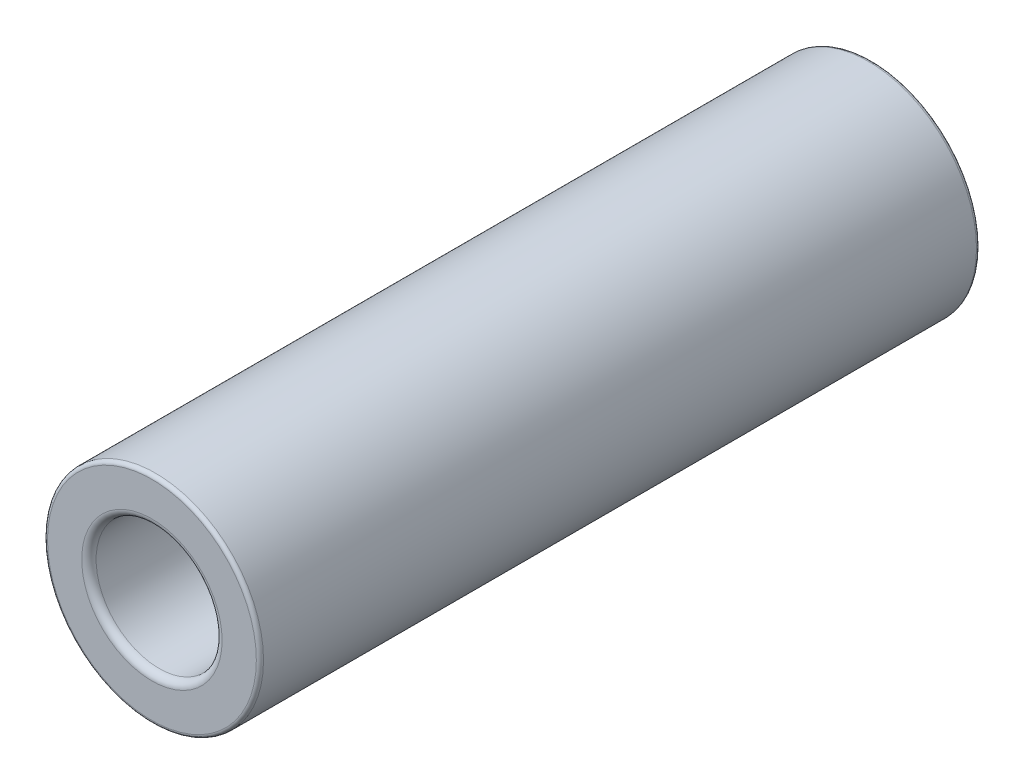
SolidWorks part; units mm, degrees
ref_plane "Alzado" through (0, 0, 0) normal (0, 0, 1) x (1, 0, 0)
ref_plane "Planta" through (0, 0, 0) normal (0, 1, 0) x (1, 0, 0)
ref_plane "Vista lateral" through (0, 0, 0) normal (1, 0, 0) x (0, 0, -1)
sketch "Croquis1" plane through (0, 0, 0) normal (0, 0, 1) x (1, 0, 0)
  circle A0 centre (0, 0) radius 1.75
  circle A1 centre (0, 0) radius 3
  dimension "D1" = 3.5
  dimension "D2" = 6
extrude "Saliente-Extruir2" add sketch "Croquis1" along normal blind 20
fillet "Redondeo5" radius 0.1 2 edges at (3, 0, 0) (3, 0, 20)
fillet "Redondeo6" radius 0.2 2 edges at (1.75, 0, 0) (1.75, 0, 20)
